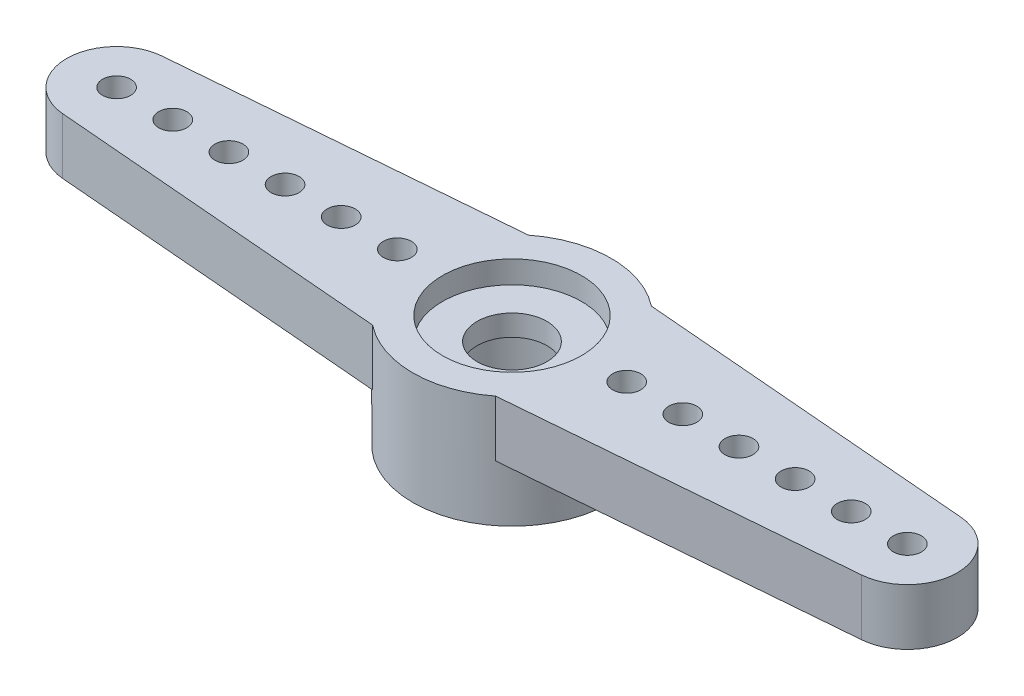
SolidWorks part; units mm, degrees
material "PA Type 6"
ref_plane "Front Plane" through (0, 0, 0) normal (0, 0, 1) x (1, 0, 0)
ref_plane "Top Plane" through (0, 0, 0) normal (0, 1, 0) x (1, 0, 0)
ref_plane "Right Plane" through (0, 0, 0) normal (1, 0, 0) x (0, 0, -1)
ref_axis "X-Axis" through (-88.99, 0, 0) along (1, 0, 0)
ref_axis "Y-Axis" through (0, 0, -88.99) along (0, 0, 1)
ref_axis "Z-Axis" through (0, 55, 0) along (0, -1, 0)
sketch "Sketch2" plane through (0, 0, 0) normal (0, 0, 1) x (1, 0, 0)
  line L0 (0, 0) -> (0, -2) construction
  line L1 (2.475, 2) -> (2.475, 1.2)
  line L2 (2.475, 1.2) -> (1.245, 1.2)
  line L3 (1.245, 1.2) -> (1.245, 0.45)
  line L4 (1.245, 0.45) -> (2.375, 0.45)
  line L5 (2.375, 0.45) -> (2.375, -2)
  line L6 (2.375, -2) -> (3.535, -2)
  line L7 (3.535, -2) -> (3.535, 2)
  line L8 (3.535, 2) -> (2.475, 2)
  dimension "D1" = 4.75
  dimension "D2" = 2.49
  dimension "D3" = 4.95
  dimension "D4" = 0.8
  dimension "D5" = 7.07
  dimension "D6" = 2
  dimension "D7" = 2.45
  dimension "D8" = 4
revolve "Revolve1" add sketch "Sketch2" angle 360 about axis through (0, 55, 0) along (0, -1, 0)
sketch "Sketch3" plane through (0, 0, 0) normal (0, 1, 0) x (1, 0, 0)
  line L0 (2.1899, -2.775) -> (14.2325, -1.7739)
  line L1 (0, 0) -> (20.2296, 0) construction
  line L2 (-3.535, 0) -> (15.865, 0) construction
  line L3 (2.1899, -2.775) -> (2.1899, 0)
  line L4 (2.1899, 0) -> (15.865, 0)
  circle A0 centre (0, 0) radius 3.535 construction
  circle A1 centre (14.085, 0) radius 1.78
  circle A2 centre (0, 0) radius 3.535
  circle A3 centre (14.085, 0) radius 0.5
  circle A4 centre (12.085, 0) radius 0.5
  circle A5 centre (10.085, 0) radius 0.5
  circle A6 centre (8.085, 0) radius 0.5
  circle A7 centre (6.085, 0) radius 0.5
  circle A8 centre (4.085, 0) radius 0.5
  point P3 (0, 0)
  dimension "D2" = 3.56
  dimension "D5" = 6
  dimension "D1" = 2.775
  dimension "D4" = 1
  dimension "D3" = 19.4
extrude "Boss-Extrude1" add sketch "Sketch3" along normal up to surface (2 mm away) contours A8 L4 A2 L0 A1 A4 A5 A6 A7 | A4 A1 L4 A3 region at (7.6377, 0, 1.3069) region at (14.1152, 0, 0.8137) up to face at (0, 2, 2.475)
mirror "Mirror1" about plane through (0, 15.9538, 0) normal (0, 0, -1) of "Boss-Extrude1"
mirror "镜向1" about plane through (0, 0, 0) normal (1, 0, 0) of "Boss-Extrude1"
mirror "镜向2" about plane through (0, 0, 0) normal (0, 0, 1) of "镜向1"
